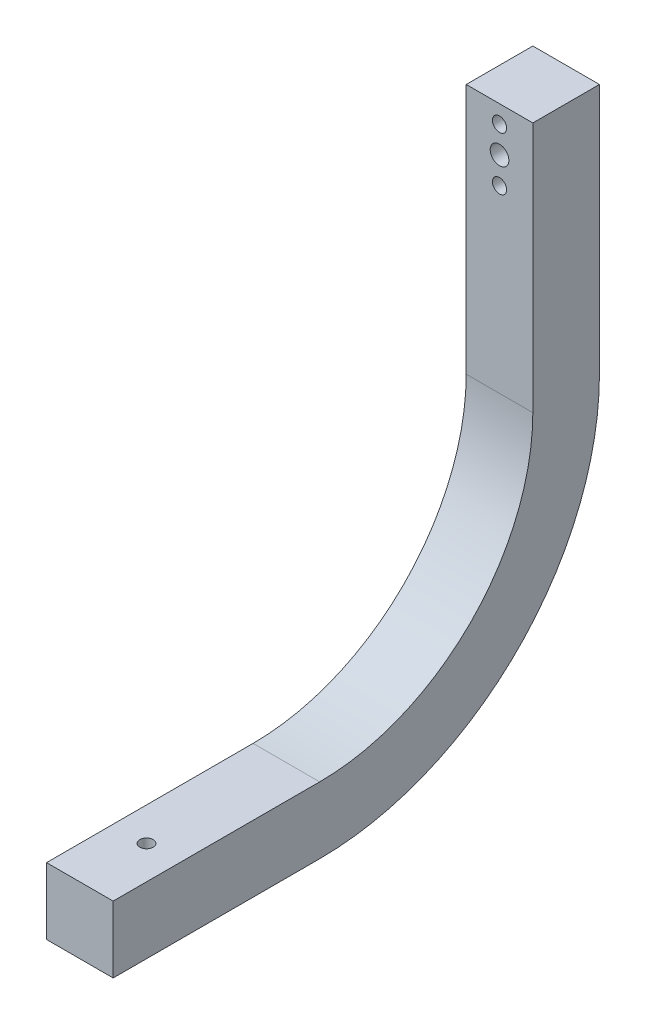
SolidWorks part; units mm, degrees
ref_plane "Front Plane" through (0, 0, 0) normal (0, 0, 1) x (1, 0, 0)
ref_plane "Top Plane" through (0, 0, 0) normal (0, 1, 0) x (1, 0, 0)
ref_plane "Right Plane" through (0, 0, 0) normal (1, 0, 0) x (0, 0, -1)
ref_axis "Z" through (0, 0, 112.875) along (0, 0, -1)
sketch "Sketch1" plane through (0, 0, 0) normal (1, 0, 0) x (0, 0, -1)
  line L0 (-15, 10) -> (0, 10)
  line L1 (0, 10) -> (0, -46.5)
  line L2 (0, -32) -> (-77.5, -109.5) construction
  line L3 (-63, -109.5) -> (-94.5, -109.5)
  line L4 (-94.5, -109.5) -> (-94.5, -94.5) construction
  line L5 (-94.5, -94.5) -> (-63, -94.5)
  line L6 (-83.7132, -94.5) -> (-15, -25.7868) construction
  line L7 (-15, -46.5) -> (-15, 10)
  line L8 (-49.3566, -60.1434) -> (-38.75, -70.75) construction
  line L9 (-63, -94.5) -> (-83.7132, -94.5) construction
  line L10 (-94.5, -94.5) -> (-109.5, -94.5)
  line L11 (-94.5, -94.5) -> (-94.5, -109.5) construction
  line L12 (-94.5, -109.5) -> (-109.5, -109.5)
  line L13 (-109.5, -94.5) -> (-109.5, -109.5)
  line L14 (-15, -25.7868) -> (-15, -46.5) construction
  line L15 (0, -46.5) -> (0, -32) construction
  line L16 (-77.5, -109.5) -> (-63, -109.5) construction
  arc A0 (-63, -94.5) -> (-15, -46.5) centre (-63, -46.5) ccw
  arc A1 (-63, -109.5) -> (0, -46.5) centre (-63, -46.5) ccw
  dimension "D1" = 15
  dimension "D2" = 94.5
  dimension "D3" = 109.5
  dimension "D4" = 10
  dimension "D5" = 135
  dimension "D6" = 77.5
  dimension "D7" = 15
  dimension "D8" = 31.5
extrude "Boss-Extrude1" add sketch "Sketch1" along normal blind 7.5 and the other way blind 7.5
sketch "Sketch3" plane through (0, -94.5, 0) normal (0, 1, 0) x (1, 0, 0)
  line L0 (-8.25, 0) -> (8.25, 0) construction
  line L1 (0, -59.125) -> (0, 59.125) construction
  circle A0 centre (0, -94.5) radius 1.5
  dimension "D2" = 3
  dimension "D1" = 94.5
extrude "Cut-Extrude1" cut sketch "Sketch3" against normal through all
sketch "Sketch4" plane through (0, 0, 15) normal (0, 0, 1) x (1, 0, 0)
  line L0 (0, -6) -> (0, 6) construction
  circle A0 centre (0, 0) radius 2.1
  circle A1 centre (0, 6) radius 1.6
  circle A2 centre (0, -6) radius 1.6
  dimension "D1" = 4.2
  dimension "D3" = 3.2
  dimension "D2" = 12
extrude "Cut-Extrude2" cut sketch "Sketch4" against normal through all both and the other way through all
ref_axis "Axis1" through (0, -94.5, 94.5) along (0, 1, 0)
sketch "Sketch5" plane through (0, -109.5, 0) normal (0, -1, 0) x (1, 0, 0)
  circle A0 centre (0, 94.5) radius 2.275
  dimension "D1" = 4.55
extrude "Cut-Extrude3" cut sketch "Sketch5" against normal blind 6
sketch "Sketch6" plane through (0, -109.5, 0) normal (0, -1, 0) x (1, 0, 0)
  circle A0 centre (0, 94.5) radius 3.825
  dimension "D1" = 7.65
extrude "Cut-Extrude4" cut sketch "Sketch6" against normal blind 0.75
equation "\"rbracket-width\"= \"L2Thickness\""
equation "\"D1@Boss-Extrude1\"=\"rbracket-width\"/2"
equation "\"D2@Boss-Extrude1\"=\"rbracket-width\"/2"
equation "\"EyeCaptureRadius\"= ( \"EyeDiameter\" + \"EyeClearance\" ) / 2"
equation "\"rbracket_planetocenterline_dist\"= \"BasePlaneDistance\""
equation "\"D2@Sketch1\"=\"rbracket_planetocenterline_dist\""
equation "\"EyeDiameter\" = 155"
equation "\"BasePlaneDistance\" = \"EyeDiameter\"/2+\"L2Thickness\"+\"EyeClearance\""
equation "\"EyeClearance\" = 2"
equation "\"D1@Sketch1\"=\"rbracket-width\""
equation "\"D3@Sketch1\"=(\"EyeDiameter\"+\"EyeClearance\"+\"EyeClearance\")/2 + \"L2Thickness\" + \"rbracket-width\""
equation "\"D4@Sketch1\"= 10"
equation "\"D6@Sketch1\"=\"EyeDiameter\"/2"
equation "\"D7@Sketch1\"=\"rbracket-width\""
equation "\"D1@Sketch3\"=\"BasePlaneDistance\""
equation "\"L2Thickness\" = 15"
equation "\"D8@Sketch1\"=\"rbracket_planetocenterline_dist\"/3"
equation "\"BearingFlangeOD\"= 7.5"
equation "\"BearingFlangeThickness\"= 0.75"
equation "\"BearingHousingID\"=4.5"
equation "\"BearingDepth\"= 6"
equation "\"D1@Sketch5\"=\"BearingHousingID\" + \"PrinterFilamentThickness\" * \"ApplyPrinterOffsets\" / 2"
equation "\"D1@Cut-Extrude3\"=\"BearingDepth\""
equation "\"D1@Sketch6\"=\"BearingFlangeOD\" + \"PrinterFilamentThickness\" * 1.5 * \"ApplyPrinterOffsets\""
equation "\"D1@Cut-Extrude4\"=\"BearingFlangeThickness\""
equation "\"PrinterFilamentThickness\"= 0.1"
equation "\"ApplyPrinterOffsets\"= 1"
